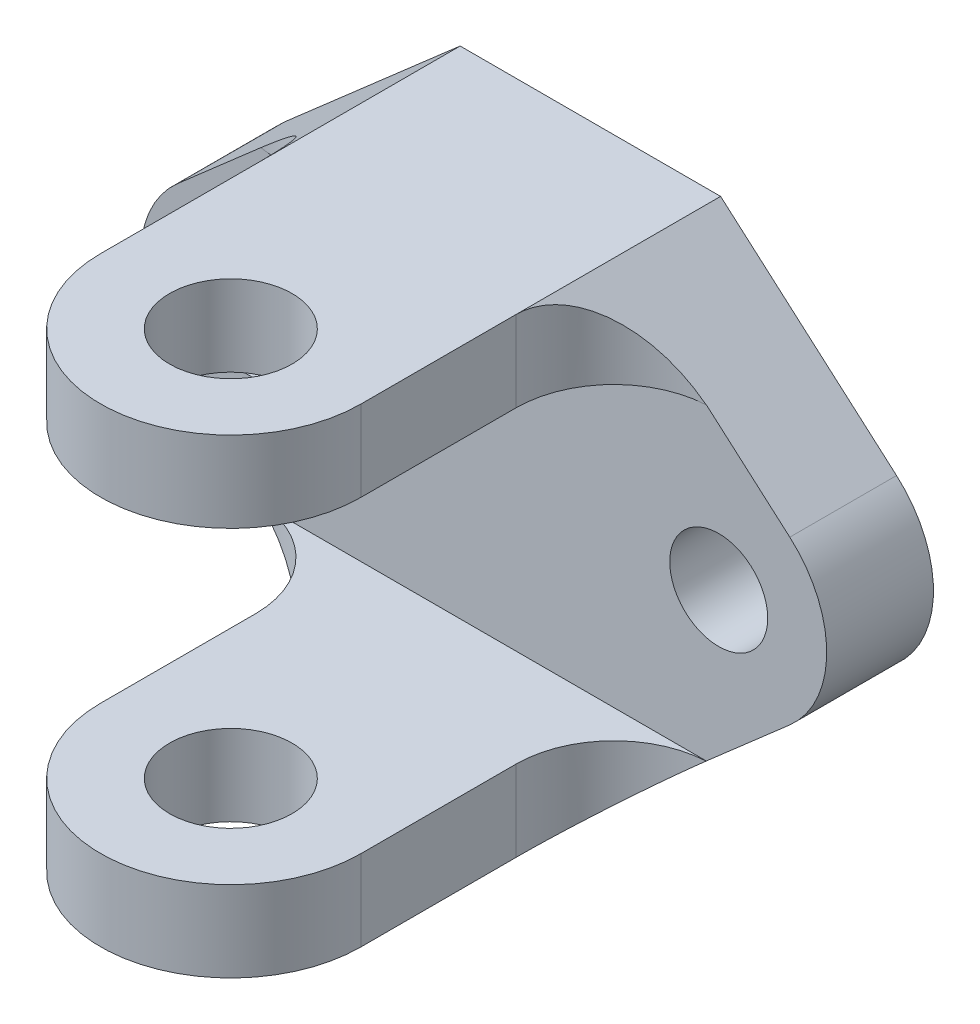
SolidWorks part; units mm, degrees
material "7075-T6 (SN)"
ref_plane "Front Plane" through (0, 0, 0) normal (0, 0, 1) x (1, 0, 0)
ref_plane "Top Plane" through (0, 0, 0) normal (0, 1, 0) x (1, 0, 0)
ref_plane "Right Plane" through (0, 0, 0) normal (1, 0, 0) x (0, 0, -1)
sketch "Sketch1" plane through (0, 0, 0) normal (0, 0, 1) x (1, 0, 0)
  line L0 (15.24, 0) -> (-15.24, 0) construction
  line L1 (-23.24, -15.24) -> (23.24, -15.24)
  line L2 (-23.24, -15.24) -> (-23.24, 15.24)
  line L3 (-23.24, 15.24) -> (23.24, 15.24)
  line L4 (23.24, -15.24) -> (23.24, 15.24)
  line L5 (-23.24, -15.24) -> (23.24, 15.24) construction
  line L6 (-23.24, 15.24) -> (23.24, -15.24) construction
  circle A0 centre (15.24, 0) radius 3.175
  circle A1 centre (-15.24, 0) radius 3.175
  point P0 (0, 0)
  dimension "D1" = 6.35
  dimension "D2" = 30.48
  dimension "D3" = 8
  dimension "D4" = 15.24
extrude "Boss-Extrude1" add sketch "Sketch1" along normal blind 9.46
sketch "Sketch2" plane through (0, 0, 9.46) normal (0, 0, 1) x (1, 0, 0)
  line L0 (-15.24, 0) -> (15.24, 0) construction
  line L2 (-23.24, 10) -> (23.24, 10)
  line L3 (-23.24, 10) -> (-23.24, 15.24)
  line L4 (-23.24, 15.24) -> (23.24, 15.24)
  line L5 (23.24, 10) -> (23.24, 15.24)
  line L6 (-23.24, 10) -> (23.24, 15.24) construction
  line L7 (-23.24, 15.24) -> (23.24, 10) construction
  line L8 (-23.24, 15.24) -> (-23.24, -15.24) construction
  line L9 (23.24, -10) -> (23.24, -15.24)
  line L10 (-23.24, -10) -> (-23.24, -15.24)
  line L11 (-23.24, -15.24) -> (23.24, -10) construction
  line L12 (-23.24, -10) -> (23.24, -15.24) construction
  line L13 (-23.24, -10) -> (23.24, -10)
  line L14 (-23.24, -15.24) -> (23.24, -15.24)
  circle A0 centre (-15.24, 0) radius 3.175 construction
  circle A1 centre (15.24, 0) radius 3.175 construction
  point P6 (0, 12.62)
  point P21 (0, -12.62)
  dimension "D1" = 20
extrude "Boss-Extrude2" add sketch "Sketch2" along normal blind 53
sketch "Sketch3" plane through (0, 0, 0) normal (0, 1, 0) x (1, 0, 0)
  point P0 (0, -25.8481)
  dimension "D1" = 25.8481
ref_point "UBJ Point"
sketch "Sketch4" plane through (0, 0, 0) normal (0, 1, 0) x (1, 0, 0)
  circle A0 centre (0, -25.8481) radius 3.9688
  dimension "D1" = 7.9375
extrude "Cut-Extrude1" cut sketch "Sketch4" against normal up to surface and the other way up to surface up to face at (0, -15.24, 31.23) other way up to face at (0, 15.24, 31.23)
sketch "Sketch5" plane through (0, 0, 0) normal (0, 1, 0) x (1, 0, 0)
  line L0 (23.24, -9.46) -> (8.2363, -31.4641)
  line L1 (-8.2363, -31.4641) -> (-23.24, -9.46)
  line L4 (23.24, 0) -> (-23.24, 0)
  line L5 (-23.24, 0) -> (-23.24, -62.46)
  line L6 (-23.24, -62.46) -> (23.24, -62.46)
  line L7 (23.24, -62.46) -> (23.24, 0)
  line L9 (-23.24, -9.46) -> (-23.24, -62.46)
  line L10 (-23.24, -62.46) -> (23.24, -62.46)
  line L11 (23.24, -62.46) -> (23.24, -9.46)
  line L12 (23.24, -9.46) -> (-23.24, -9.46)
  line L13 (23.24, -62.46) -> (23.24, -9.46)
  line L14 (-23.24, -62.46) -> (23.24, -62.46)
  line L15 (-23.24, -9.46) -> (-23.24, -62.46)
  line L17 (23.24, -62.46) -> (23.24, -9.46)
  line L18 (-23.24, -62.46) -> (23.24, -62.46)
  line L19 (-23.24, -9.46) -> (-23.24, -62.46)
  arc A0 (-8.2363, -31.4641) -> (8.2363, -31.4641) centre (0, -25.8481) ccw
  circle A1 centre (0, -25.8481) radius 3.9688 construction
  circle A2 centre (0, -25.8481) radius 3.9688 construction
  dimension "D3" = 6
  dimension "D1" = 0
  dimension "D2" = 0
extrude "Cut-Extrude2" [suppressed] cut sketch "Sketch5" against normal up to surface and the other way up to surface contours A0 L1 L9 L10 L11 L0
sketch "Sketch6" plane through (0, 0, 0) normal (0, 1, 0) x (1, 0, 0)
  line L0 (-8.4419, -25.8481) -> (-8.4419, -17.46)
  line L1 (8.4419, -25.8481) -> (8.4419, -17.46)
  line L2 (-16.4419, -9.46) -> (-23.24, -9.46)
  line L3 (-8.4419, -17.46) -> (-8.4419, -9.46)
  line L4 (23.24, -9.46) -> (-23.24, -9.46)
  line L5 (-23.24, -9.46) -> (-23.24, -62.46)
  line L6 (-23.24, -62.46) -> (23.24, -62.46)
  line L7 (23.24, -62.46) -> (23.24, -9.46)
  line L8 (23.24, -9.46) -> (16.4419, -9.46)
  line L9 (-23.24, -9.46) -> (-23.24, -62.46)
  line L10 (-23.24, -62.46) -> (23.24, -62.46)
  line L11 (23.24, -62.46) -> (23.24, -9.46)
  line L12 (-8.4419, -9.46) -> (-16.4419, -9.46)
  line L13 (8.4419, -17.46) -> (8.4419, -9.46)
  line L14 (8.4419, -9.46) -> (16.4419, -9.46)
  line L15 (-9.5959, -34.29) -> (9.5959, -34.29) construction
  line L16 (23.24, 0) -> (-23.24, 0) construction
  arc A0 (-8.4419, -25.8481) -> (8.4419, -25.8481) centre (0, -25.8481) ccw
  circle A1 centre (0, -25.8481) radius 3.9688 construction
  arc A2 (-8.4419, -17.46) -> (-16.4419, -9.46) centre (-16.4419, -17.46) ccw construction
  arc A3 (8.4419, -17.46) -> (16.4419, -9.46) centre (16.4419, -17.46) cw construction
  point P19 (0, -34.29)
  dimension "D2" = 34.29
  dimension "D3" = 8
  dimension "D1" = 0
extrude "Cut-Extrude3" cut sketch "Sketch6" against normal up to surface and the other way up to surface contours A0 L3 L12 L2 L9 L10 L11 L8 L14 L13 region at (0, 0, 38.7535) up to face at (0, -15.24, 29.8169) other way up to face at (0, 15.24, 21.8794)
fillet "Fillet1" [suppressed] radius 12.7
sketch "Sketch7" plane through (0, 0, 0) normal (0, 0, 1) x (1, 0, 0)
  line L0 (-15.24, 7) -> (-8.4419, 7)
  line L1 (-15.24, -7) -> (-8.4419, -7)
  line L2 (-8.4419, 10) -> (-8.4419, 7)
  line L3 (-8.4419, -10) -> (-8.4419, -7)
  line L4 (0, 10.3988) -> (0, -8.4154) construction
  line L5 (8.4419, -10) -> (8.4419, -7)
  line L6 (8.4419, 10) -> (8.4419, 15.24)
  line L7 (23.24, 15.24) -> (23.24, -15.24)
  line L8 (8.4419, -10) -> (8.4419, -15.24)
  line L9 (8.4419, 10) -> (8.4419, 7)
  line L10 (15.24, 7) -> (8.4419, 7)
  line L11 (15.24, -7) -> (8.4419, -7)
  line L12 (8.4419, 10) -> (-8.4419, 10)
  line L15 (-23.24, 15.24) -> (-23.24, -15.24)
  line L18 (-8.4419, -10) -> (8.4419, -10)
  line L21 (23.24, -15.24) -> (23.24, 15.24)
  line L27 (-23.24, 15.24) -> (-23.24, -15.24)
  line L33 (23.24, -15.24) -> (23.24, 15.24)
  line L36 (-8.4419, 15.24) -> (-8.4419, 10)
  line L37 (-8.4419, -10) -> (-8.4419, -15.24)
  line L48 (-8.4419, 10) -> (-8.4419, 15.24)
  line L49 (-8.4419, -15.24) -> (-8.4419, -10)
  line L52 (-8.4419, 15.24) -> (-23.24, 15.24)
  line L53 (-8.4419, 15.24) -> (-23.24, 15.24)
  line L54 (-23.24, -15.24) -> (-8.4419, -15.24)
  line L55 (-23.24, -15.24) -> (-8.4419, -15.24)
  line L56 (8.4419, -10) -> (8.4419, -15.24)
  line L57 (8.4419, -15.24) -> (23.24, -15.24)
  line L58 (8.4419, -15.24) -> (23.24, -15.24)
  line L59 (23.24, 15.24) -> (8.4419, 15.24)
  line L60 (23.24, 15.24) -> (8.4419, 15.24)
  line L61 (8.4419, 15.24) -> (8.4419, 10)
  arc A0 (-15.24, 7) -> (-15.24, -7) centre (-15.24, 0) ccw
  circle A1 centre (-15.24, 0) radius 3.175 construction
  arc A2 (15.24, 7) -> (15.24, -7) centre (15.24, 0) cw
  dimension "D2" = 7
  dimension "D1" = 0
extrude "Cut-Extrude4" cut sketch "Sketch7" along normal up to surface (9.46 mm away) contours A0 L0 L2 L53 L27 L55 L3 L1 | L10 A2 L11 L5 L7 L9 region at (-22.5788, 0, 0) region at (8.7807, 12.62, 0) up to face at (18.415, 0, 9.46)
fillet "Fillet2" [suppressed] radius 5
sketch "Sketch8" plane through (0, 0, 0) normal (0, 0, 1) x (1, 0, 0)
  line L0 (15.24, 7) -> (8.4419, 7) construction
  line L1 (8.4419, 15.24) -> (8.4419, 7) construction
  line L2 (15.24, 7) -> (8.4419, 7)
  line L3 (8.4419, 15.24) -> (8.4419, 7)
  line L4 (6.7586, 0) -> (-5.803, 0) construction
  line L5 (0, 7.1591) -> (0, -7.1591) construction
  line L6 (8.4419, 15.24) -> (19.847, 5.2703)
  line L7 (-8.4419, 15.24) -> (-8.4419, 7)
  line L8 (-15.24, 7) -> (-8.4419, 7)
  line L9 (-8.4419, 15.24) -> (-19.847, 5.2703)
  line L10 (-8.4419, -15.24) -> (-19.847, -5.2703)
  line L11 (-15.24, -7) -> (-8.4419, -7)
  line L12 (-8.4419, -15.24) -> (-8.4419, -7)
  line L13 (8.4419, -15.24) -> (8.4419, -7)
  line L14 (15.24, -7) -> (8.4419, -7)
  line L15 (8.4419, -15.24) -> (19.847, -5.2703)
  arc A0 (15.24, -7) -> (15.24, 7) centre (15.24, 0) ccw construction
  arc A1 (19.847, 5.2703) -> (15.24, 7) centre (15.24, 0) ccw
  arc A2 (-19.847, 5.2703) -> (-15.24, 7) centre (-15.24, 0) cw
  arc A3 (-19.847, -5.2703) -> (-15.24, -7) centre (-15.24, 0) ccw
  arc A4 (19.847, -5.2703) -> (15.24, -7) centre (15.24, 0) cw
extrude "Boss-Extrude3" add sketch "Sketch8" along normal up to surface (9.46 mm away) contours L15 A4 L14 L13 | A3 L10 L12 L11 | L6 A1 L2 L3 | L9 A2 L8 L7 region at (-11.7078, -9.6842, 0) region at (11.7078, -9.6842, 0) up to face at (0, 0, 9.46)
fillet "Fillet3" radius 6.35 4 edges at (8.4419, 12.62, 9.46) (-8.4419, 12.62, 9.46) (8.4419, -12.62, 9.46) (-8.4419, -12.62, 9.46)
sketch "Sketch10" plane through (0, 0, 0) normal (0, 0, 1) x (1, 0, 0)
  line L5 (-8.4419, 15.24) -> (-19.847, 5.2703)
  line L6 (-8.4419, 15.24) -> (-19.847, 5.2703)
  line L7 (8.4419, 15.24) -> (-8.4419, 15.24)
  line L8 (19.847, 5.2703) -> (8.4419, 15.24)
  line L9 (8.4419, -15.24) -> (19.847, -5.2703)
  line L10 (-8.4419, -15.24) -> (8.4419, -15.24)
  line L13 (8.4419, 15.24) -> (-8.4419, 15.24)
  line L14 (19.847, 5.2703) -> (8.4419, 15.24)
  line L15 (8.4419, -15.24) -> (19.847, -5.2703)
  line L16 (-8.4419, -15.24) -> (8.4419, -15.24)
  line L18 (-19.847, -5.2703) -> (-8.4419, -15.24)
  line L19 (-19.847, -5.2703) -> (-8.4419, -15.24)
  arc A2 (-19.847, 5.2703) -> (-19.847, -5.2703) centre (-15.24, 0) ccw
  arc A3 (19.847, -5.2703) -> (19.847, 5.2703) centre (15.24, 0) ccw
  arc A5 (19.847, -5.2703) -> (19.847, 5.2703) centre (15.24, 0) ccw
  arc A6 (-19.847, 5.2703) -> (-19.847, -5.2703) centre (-15.24, 0) ccw
  dimension "D1" = 0
extrude "Cut-Extrude5" cut sketch "Sketch10" along normal blind 2.54
